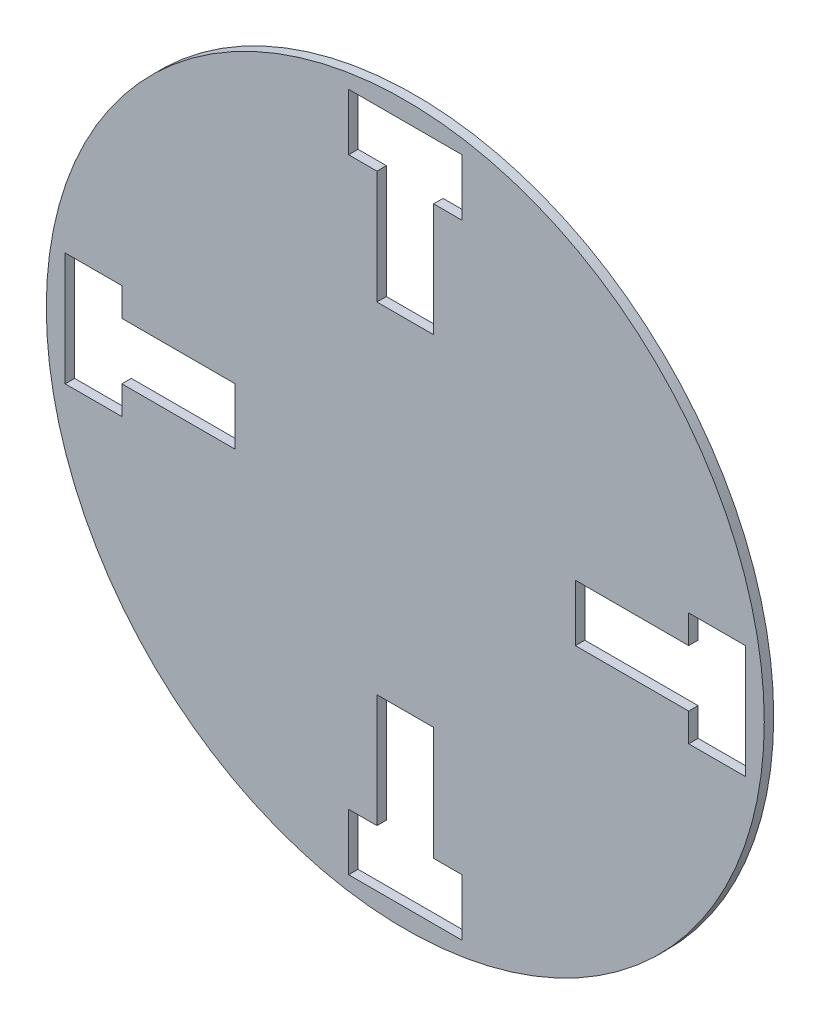
SolidWorks part; units mm, degrees
ref_plane "Plan de face" through (0, 0, 0) normal (0, 0, 1) x (1, 0, 0)
ref_plane "Plan de dessus" through (0, 0, 0) normal (0, 1, 0) x (1, 0, 0)
ref_plane "Plan de droite" through (0, 0, 0) normal (1, 0, 0) x (0, 0, -1)
sketch "Esquisse1" plane through (0, 0, 0) normal (0, 0, 1) x (1, 0, 0)
  circle A0 centre (0, 0) radius 190
  dimension "D1" = 380
extrude "Boss.-Extru.1" add sketch "Esquisse1" against normal blind 5
sketch "Esquisse2" plane through (0, 0, 0) normal (0, 0, 1) x (1, 0, 0)
  line L4 (-15, 150) -> (-15, 90)
  line L5 (0, 190) -> (0, -190) construction
  line L6 (-190, 0) -> (190, 0) construction
  line L7 (-30, 180) -> (30, 180)
  line L8 (-30, 180) -> (-30, 150)
  line L10 (30, 180) -> (30, 150)
  line L11 (-15, 90) -> (15, 90)
  line L12 (15, 90) -> (15, 150)
  line L13 (-15, 150) -> (-30, 150)
  line L14 (30, 150) -> (15, 150)
  line L15 (30, -180) -> (30, -150)
  line L16 (-30, -180) -> (30, -180)
  line L17 (-30, -180) -> (-30, -150)
  line L18 (-15, -150) -> (-30, -150)
  line L19 (-15, -150) -> (-15, -90)
  line L20 (-15, -90) -> (15, -90)
  line L21 (15, -90) -> (15, -150)
  line L22 (30, -150) -> (15, -150)
  line L23 (0, 0) -> (134.3503, 134.3503) construction
  line L24 (180, 30) -> (150, 30)
  line L25 (180, -30) -> (180, 30)
  line L26 (180, -30) -> (150, -30)
  line L27 (150, -15) -> (150, -30)
  line L28 (150, -15) -> (90, -15)
  line L29 (90, -15) -> (90, 15)
  line L30 (90, 15) -> (150, 15)
  line L31 (150, 30) -> (150, 15)
  line L32 (0, 0) -> (-134.3503, 134.3503) construction
  line L33 (-180, -30) -> (-150, -30)
  line L34 (-180, 30) -> (-180, -30)
  line L35 (-180, 30) -> (-150, 30)
  line L36 (-150, 15) -> (-150, 30)
  line L37 (-150, 15) -> (-90, 15)
  line L38 (-90, 15) -> (-90, -15)
  line L39 (-90, -15) -> (-150, -15)
  line L40 (-150, -30) -> (-150, -15)
  circle A0 centre (0, 0) radius 190 construction
  point P13 (0, 90)
  dimension "D1" = 30
  dimension "D2" = 60
  dimension "D3" = 60
  dimension "D4" = 30
  dimension "D5" = 150
  dimension "D6" = 180
  dimension "D7" = 45
extrude "Enlèv. mat.-Extru.1" cut sketch "Esquisse2" against normal blind 5
